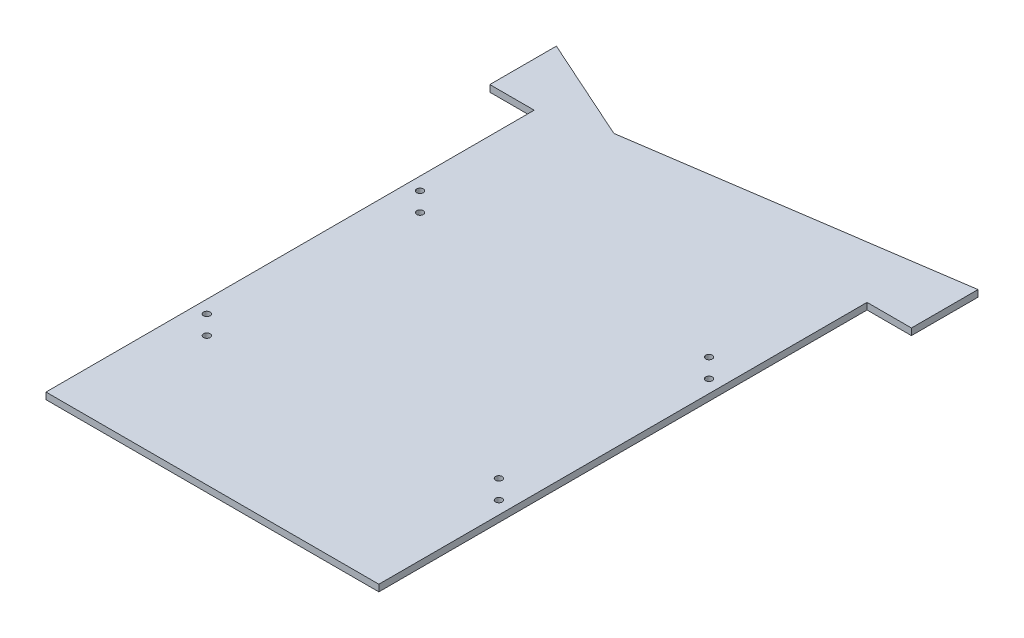
SolidWorks part; units mm, degrees
ref_plane "Front Plane" through (0, 0, 0) normal (0, 0, 1) x (1, 0, 0)
ref_plane "Top Plane" through (0, 0, 0) normal (0, 1, 0) x (1, 0, 0)
ref_plane "Right Plane" through (0, 0, 0) normal (1, 0, 0) x (0, 0, -1)
sketch "Sketch1" plane through (0, 0, 0) normal (0, 1, 0) x (1, 0, 0)
  line L1 (-75, -100) -> (75, -100)
  line L2 (-75, -100) -> (-75, 100)
  line L3 (-75, 100) -> (75, 100)
  line L4 (75, -100) -> (75, 100)
  line L5 (-75, -100) -> (75, 100) construction
  line L6 (-75, 100) -> (75, -100) construction
  circle A0 centre (-69.2426, 62.7961) radius 1.5
  circle A1 centre (-60.7574, 54.3108) radius 1.5
  circle A2 centre (60.7574, 63.0348) radius 1.5
  circle A3 centre (69.2426, 54.5495) radius 1.5
  circle A4 centre (-69.2426, -33.2742) radius 1.5
  circle A5 centre (-60.7574, -41.7595) radius 1.5
  circle A6 centre (60.7574, -31.6419) radius 1.5
  circle A7 centre (69.2426, -40.1271) radius 1.5
  point P0 (0, 0)
  dimension "D1" = 150
  dimension "D2" = 200
extrude "Boss-Extrude1" add sketch "Sketch1" along normal blind 3
sketch "Sketch2" plane through (0, 3, 0) normal (0, 1, 0) x (1, 0, 0)
  line L8 (-75, 100) -> (-75, 120)
  line L9 (-75, 120) -> (-95, 120)
  line L10 (-95, 120) -> (-95, 150)
  line L11 (-95, 150) -> (-48, 128.8958)
  line L12 (-48, 128.8958) -> (95, 150)
  line L13 (95, 150) -> (95, 120)
  line L14 (95, 120) -> (75, 120)
  line L15 (75, 120) -> (75, 100)
  line L20 (-75, 100) -> (75, 100)
  dimension "D2" = 30
  dimension "D3" = 27
  dimension "D4" = 20
  dimension "D1" = 20
extrude "Boss-Extrude3" add sketch "Sketch2" against normal blind 3
